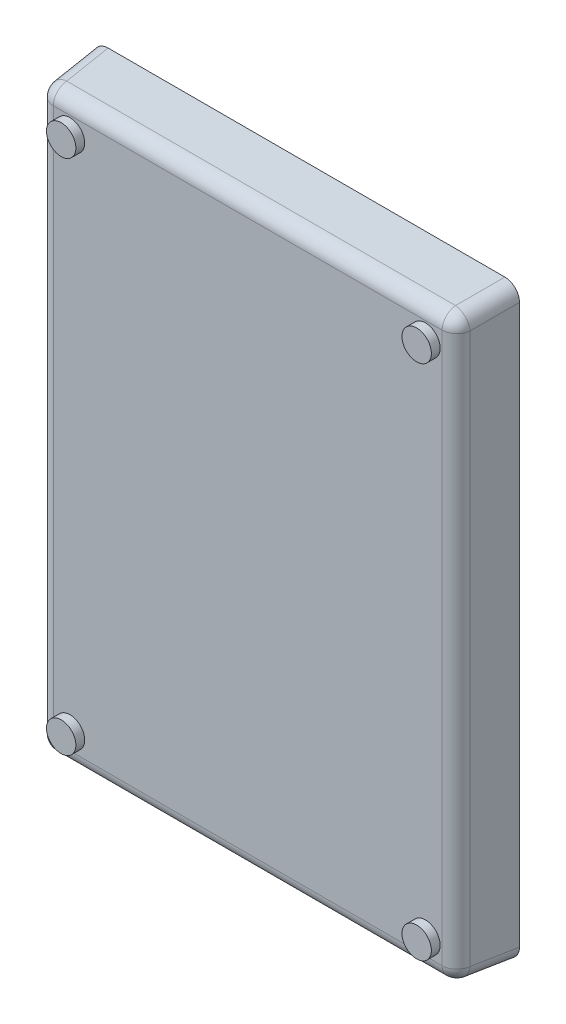
SolidWorks part; units mm, degrees
ref_plane "Спереди" through (0, 0, 0) normal (0, 0, 1) x (1, 0, 0)
ref_plane "Сверху" through (0, 0, 0) normal (0, 1, 0) x (1, 0, 0)
ref_plane "Справа" through (0, 0, 0) normal (1, 0, 0) x (0, 0, -1)
sketch "Sketch1" plane through (0, 0, 0) normal (0, 0, 1) x (1, 0, 0)
  line L0 (0, 100) -> (0, -100) construction
  line L1 (72.5, -100) -> (-72.5, -100)
  line L2 (72.5, -100) -> (72.5, 100)
  line L3 (72.5, 100) -> (-72.5, 100)
  line L4 (-72.5, -100) -> (-72.5, 100)
  line L5 (-72.5, 0) -> (72.5, 0) construction
  dimension "D1" = 145
  dimension "D2" = 200
extrude "Boss-Extrude1" add sketch "Sketch1" along normal blind 20 draft 5
fillet "Fillet1" radius 5 4 edges at (71.6251, -99.1251, 10) (-71.6251, -99.1251, 10) (71.6251, 99.1251, 10) (-71.6251, 99.1251, 10)
fillet "Fillet2" radius 5 8 edges at (-69.2936, 96.7936, 20) (0, 98.2502, 20) (69.2936, 96.7936, 20) (70.7502, 0, 20) (69.2936, -96.7936, 20) (0, -98.2502, 20) (-69.2936, -96.7936, 20) (-70.7502, 0, 20)
shell "Shell1" thickness 3 removed face at (0, 0, 0)
sketch "Sketch2" plane through (0, 0, 0) normal (0, 0, -1) x (-1, 0, 0)
  line L0 (0, 106.4415) -> (0, -112.4416) construction
  line L1 (-89.0412, 0) -> (89.7612, 0) construction
  circle A0 centre (-60.5, 88) radius 5
  circle A1 centre (60.5, 88) radius 5
  circle A2 centre (-60.5, -88) radius 5
  circle A3 centre (60.5, -88) radius 5
  dimension "D1" = 121
  dimension "D3" = 10
  dimension "D2" = 176
extrude "Boss-Extrude2" add sketch "Sketch2" against normal up to surface (17 mm away) up to face at (0, 0, 17)
sketch "Sketch3" plane through (0, 0, 20) normal (0, 0, 1) x (1, 0, 0)
  circle A0 centre (60.5, -88) radius 5 construction
  circle A1 centre (-60.5, -88) radius 5 construction
  circle A2 centre (60.5, 88) radius 5 construction
  circle A3 centre (-60.5, 88) radius 5 construction
  circle A4 centre (60.5, -88) radius 5
  circle A5 centre (-60.5, -88) radius 5
  circle A6 centre (60.5, 88) radius 5
  circle A7 centre (-60.5, 88) radius 5
extrude "Boss-Extrude3" add sketch "Sketch3" along normal blind 3
